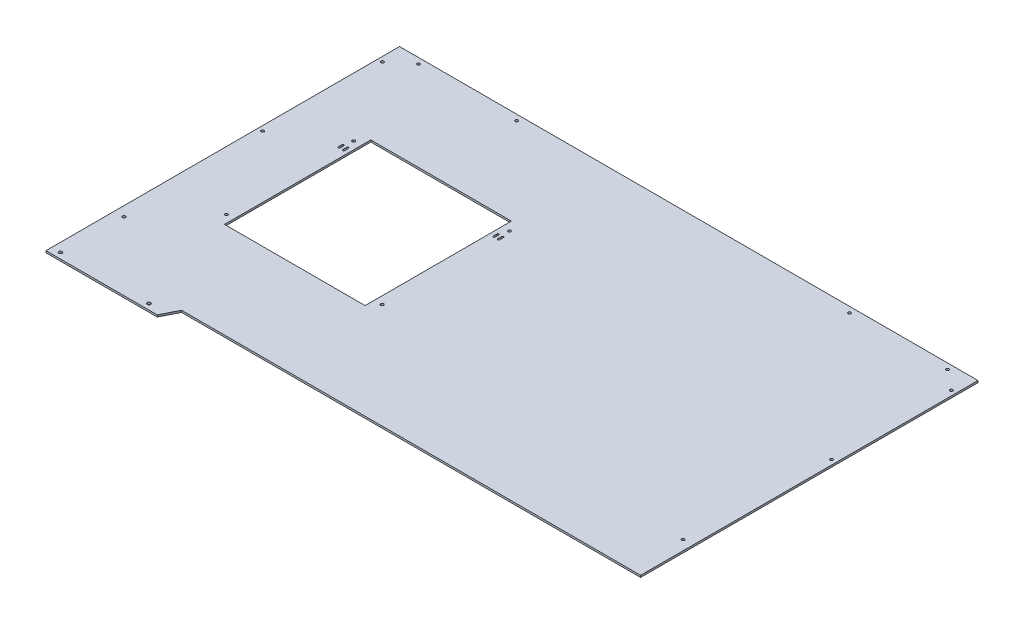
SolidWorks part; units mm, degrees
ref_plane "前视基准面" through (0, 0, 0) normal (0, 0, 1) x (1, 0, 0)
ref_plane "上视基准面" through (0, 0, 0) normal (0, 1, 0) x (1, 0, 0)
ref_plane "右视基准面" through (0, 0, 0) normal (1, 0, 0) x (0, 0, -1)
other "Configuration Table"
sketch "草图1" plane through (0, 0, 0) normal (0, 1, 0) x (1, 0, 0)
  line L0 (0, 0) -> (0, 372.1)
  line L1 (0, 372.1) -> (608.8, 372.1)
  line L2 (608.8, 372.1) -> (608.8, 17)
  line L3 (608.8, 17) -> (125.65, 17)
  line L4 (125.65, 17) -> (117.15, 0)
  line L5 (117.15, 0) -> (0, 0)
  dimension "D1" = 372.1
  dimension "D2" = 117.15
  dimension "D3" = 355.1
  dimension "D4" = 608.8
  dimension "D5" = 483.15
extrude "凸台-拉伸1" add sketch "草图1" along normal blind 2
sketch "草图2" plane through (0, 2, 0) normal (0, 1, 0) x (1, 0, 0)
  line L0 (0, 194.55) -> (43.6008, 194.55) construction
  line L1 (0, 372.1) -> (608.8, 372.1) construction
  line L2 (0, 372.1) -> (0, 17) construction
  line L3 (0, 17) -> (608.8, 17) construction
  line L4 (608.8, 372.1) -> (608.8, 17) construction
  line L5 (304.4, 372.1) -> (304.4, 331.0376) construction
  line L6 (26, 366.1) -> (35.088, 366.1) construction
  line L7 (0, 372.1) -> (0, 0) construction
  line L8 (0, 0) -> (117.15, 0) construction
  line L9 (9.2, 6) -> (12.9381, 6) construction
  line L11 (70, 271.85) -> (75, 271.85)
  line L12 (70, 271.85) -> (70, 117.85)
  line L13 (70, 117.85) -> (218, 117.85)
  line L14 (218, 271.85) -> (218, 117.85)
  line L15 (70, 271.85) -> (218, 117.85) construction
  line L16 (70, 117.85) -> (218, 271.85) construction
  line L20 (184, 271.85) -> (218, 271.85)
  line L24 (94, 271.85) -> (155, 271.85)
  line L25 (75, 271.85) -> (94, 271.85)
  line L26 (155, 271.85) -> (184, 271.85)
  line L27 (674.4766, 198.25) -> (-190.4209, 198.25) construction
  circle A0 centre (5, 349.1) radius 1.525
  circle A1 centre (26, 366.1) radius 1.525
  circle A2 centre (129.25, 366.1) radius 1.525
  circle A3 centre (5, 223.05) radius 1.525
  circle A4 centre (603.8, 223.05) radius 1.525
  circle A5 centre (479.55, 366.1) radius 1.525
  circle A6 centre (582.8, 366.1) radius 1.525
  circle A7 centre (603.8, 349.1) radius 1.525
  circle A8 centre (10.2, 71.95) radius 1.525
  circle A9 centre (598.6, 71.95) radius 1.525
  circle A10 centre (9.2, 6) radius 1.75
  circle A11 centre (102.4, 6) radius 1.75
  circle A12 centre (62, 261.85) radius 1.525
  circle A13 centre (62, 127.85) radius 1.525
  circle A15 centre (226, 261.85) radius 1.525
  circle A16 centre (226, 127.85) radius 1.525
  point P42 (144, 194.85)
  point P47 (184, 271.85)
  point P48 (155, 271.85)
  point P53 (75, 271.85)
  point P54 (94, 271.85)
  dimension "D1" = 3.05
  dimension "D5" = 3.05
  dimension "D7" = 3.05
  dimension "D9" = 3.05
  dimension "D12" = 3.05
  dimension "D15" = 3.5
  dimension "D18" = 3.5
  dimension "D30" = 3.05
  dimension "D31" = 8
  dimension "D2" = 23
  dimension "D3" = 5
  dimension "D4" = 26
  dimension "D6" = 6
  dimension "D8" = 175.15
  dimension "D10" = 5
  dimension "D11" = 28.5
  dimension "D13" = 122.6
  dimension "D14" = 10.2
  dimension "D16" = 9.2
  dimension "D17" = 6
  dimension "D19" = 93.2
  dimension "D20" = 148
  dimension "D21" = 154
  dimension "D22" = 76.7
  dimension "D23" = 70
  dimension "D24" = 34
  dimension "D25" = 63
  dimension "D26" = 149.05
  dimension "D27" = 5
  dimension "D28" = 24
  dimension "D29" = 173.85
  dimension "D32" = 8
  dimension "D33" = 10
  dimension "D34" = 10
  dimension "D35" = 8
  dimension "D36" = 8
  dimension "D37" = 10
  dimension "D38" = 10
  dimension "D39" = 126.3
extrude "切除-拉伸1" cut sketch "草图2" against normal blind 2
sketch "草图3" plane through (0, 2, 0) normal (0, 1, 0) x (1, 0, 0)
  line L0 (70, 271.85) -> (70, 117.85) construction
  line L1 (64, 253.3305) -> (66, 253.3305)
  line L2 (64, 253.3305) -> (64, 247.3305)
  line L3 (64, 247.3305) -> (66, 247.3305)
  line L4 (66, 253.3305) -> (66, 247.3305)
  line L5 (59.1324, 253.3305) -> (61.1324, 253.3305)
  line L6 (59.1324, 253.3305) -> (59.1324, 247.3305)
  line L7 (59.1324, 247.3305) -> (61.1324, 247.3305)
  line L8 (61.1324, 253.3305) -> (61.1324, 247.3305)
  line L9 (226.8676, 253.6477) -> (228.8676, 253.6477)
  line L10 (226.8676, 253.6477) -> (226.8676, 247.6477)
  line L11 (226.8676, 247.6477) -> (228.8676, 247.6477)
  line L12 (228.8676, 253.6477) -> (228.8676, 247.6477)
  line L13 (222, 253.6477) -> (224, 253.6477)
  line L14 (222, 253.6477) -> (222, 247.6477)
  line L15 (222, 247.6477) -> (224, 247.6477)
  line L16 (224, 253.6477) -> (224, 247.6477)
  line L17 (218, 117.85) -> (218, 271.85) construction
  dimension "D1" = 2
  dimension "D2" = 6
  dimension "D3" = 4
  dimension "D4" = 0
  dimension "D5" = 2.8676
  dimension "D6" = 0
  dimension "D7" = 4
extrude "切除-拉伸2" cut sketch "草图3" against normal blind 10
fillet "圆角2" radius 1 16 edges at (61.1324, 1, -247.3305) (59.1324, 1, -247.3305) (66, 1, -247.3305) (64, 1, -247.3305) (59.1324, 1, -253.3305) (61.1324, 1, -253.3305) (228.8676, 1, -247.6477) (222, 1, -247.6477) (228.8676, 1, -253.6477) (224, 1, -253.6477) (226.8676, 1, -253.6477) (222, 1, -253.6477) (64, 1, -253.3305) (66, 1, -253.3305) (224, 1, -247.6477) (226.8676, 1, -247.6477)
